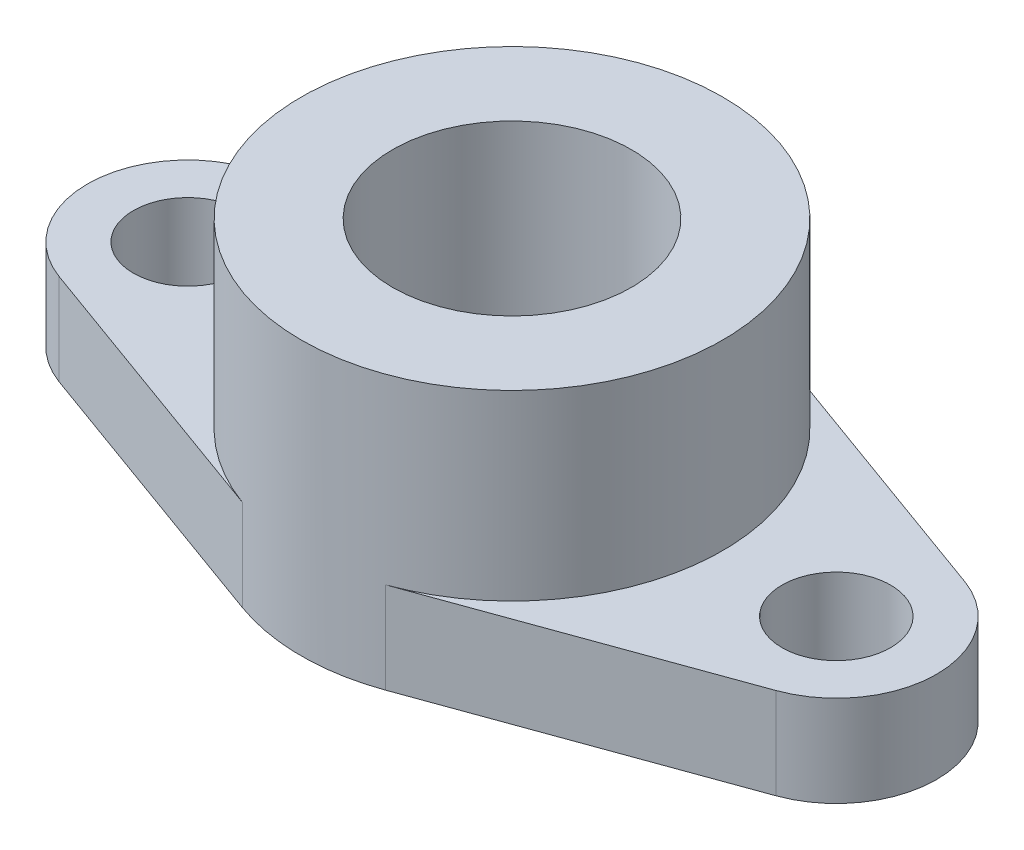
SolidWorks part; units mm, degrees
ref_plane "Front Plane" through (0, 0, 0) normal (0, 0, 1) x (1, 0, 0)
ref_plane "Top Plane" through (0, 0, 0) normal (0, 1, 0) x (1, 0, 0)
ref_plane "Right Plane" through (0, 0, 0) normal (1, 0, 0) x (0, 0, -1)
sketch "Sketch1" plane through (0, 0, 0) normal (0, 1, 0) x (1, 0, 0)
  line L0 (0, 0) -> (6.5484, 0) construction
  line L1 (0, 0) -> (17.78, 0) construction
  line L2 (19.651, 5.172) -> (3.9286, 10.8597)
  line L3 (3.9286, -10.8597) -> (19.651, -5.172)
  line L4 (0, 0) -> (-17.78, 0) construction
  line L5 (-19.651, 5.172) -> (-3.9286, 10.8597)
  line L6 (-19.651, -5.172) -> (-3.9286, -10.8597)
  circle A0 centre (0, 0) radius 4.826
  circle A1 centre (0, 0) radius 6.5484 construction
  arc A2 (3.9286, 10.8597) -> (3.9286, -10.8597) centre (0, 0) ccw construction
  circle A3 centre (17.78, 0) radius 2.9766
  arc A4 (19.651, -5.172) -> (19.651, 5.172) centre (17.78, 0) ccw
  circle A5 centre (0, 0) radius 11.5484 construction
  circle A6 centre (-17.78, 0) radius 2.9766
  arc A7 (-19.651, 5.172) -> (-19.651, -5.172) centre (-17.78, 0) ccw
  arc A10 (-3.9286, -10.8597) -> (3.9286, -10.8597) centre (0, 0) ccw
  arc A11 (3.9286, 10.8597) -> (-3.9286, 10.8597) centre (0, 0) ccw
  dimension "D1" = 9.652
  dimension "D2" = 13.0969
  dimension "D3" = 23.0969
  dimension "D5" = 5.9531
  dimension "D7" = 5.9531
  dimension "D6" = 5.5
  dimension "D4" = 17.78
  dimension "D8" = 17.78
extrude "Boss-Extrude1" add sketch "Sketch1" along normal blind 5
sketch "Sketch2" plane through (0, 5, 0) normal (0, 1, 0) x (1, 0, 0)
  circle A0 centre (0, 0) radius 11.5484
  arc A1 (-3.9286, -10.8597) -> (3.9286, -10.8597) centre (0, 0) ccw construction
  circle A2 centre (0, 0) radius 6.5484
  dimension "D1" = 13.0969
extrude "Boss-Extrude2" add sketch "Sketch2" along normal blind 10
equation "\"z\" = 8\t\t\t\t'number of blades"
equation "\"de\" = 0.43in\t\t\t'entrance eye diameter"
equation "\"de_length\" = 10mm\t\t'entrance eye consistent length"
equation "\"d_exit\" = 0.18in \t\t'throat aka d1"
equation "\"d2\" = 2.1in \t\t\t'outer diameter of the impeller"
equation "\"b2\" = .2in\t\t\t'tip height from disc surface at d2; slightly higher than d_exit"
equation "\"b1\" = \"b2\" + (\"d2\"/2 - \"de\"/2)*tan(\"theta\") \t\t\t'tip height from disc surface at inlet eye"
equation "\"theta\" = 12\t\t\t'angle of blades from inner to outer "
equation "\"ae\" = 3.14*(\"de\"^2)/4\t\t'entrance eye area'"
equation "\"ce\" = 3.14*\"de\"\t\t'entrance eye circumference"
equation "\"av_ratio\" = .325\t\t'ratio of av/ae at N_s of 470, range is .275 to .375, .325 ideal. High ratio means bigger area means smaller blades"
equation "\"av\" = \"ae\"*\"av_ratio\"\t\t'area between just two blades"
equation "\"s_open\" = \"av\"/\"b1\"\t\t'width of open area"
equation "\"s\"=\"ce\" - \"z\"*\"s_open\""
equation "\"min blade thickness\" = .15in"
equation "\"bearing OD\" = 30mm"
equation "\"bearing ID\"= 10mm"
equation "\"bearing depth\"= 9mm"
equation "\"bearing outer race thickness\"= 1mm"
equation "\"bearing inner race thickness\"= 1mm"
equation "\"bearing bore\" = \"bearing depth\" + 1mm"
equation "\"lower seal OD\" = .917in\t\t'this is https://www.mcmaster.com/#9281k121/=174001b"
equation "\"lower seal ID\"= .375in"
equation "\"lower seal depth\" = .625in + .218in"
equation "\"lower seal bore\" = \"lower seal depth\" + 1mm"
equation "\"upper seal OD\" = 1.125in\t'this is https://www.mcmaster.com/#5154t33/=173zuau, needs to be visually inspected before machining!"
equation "\"upper seal ID\"= 0.625in"
equation "\"upper seal depth\"= .25in\t'aka height; these values need to be confirmed by inspection!! We may want to compress the height."
equation "\"upper seal bore\" = \"upper seal depth\" + 1mm"
equation "\"big o-ring thickness\" = .139in"
equation "\"big o-ring OD\" = 2.734in"
equation "\"big o-ring ID\" = 3.012in"
equation "\"big o-ring groove depth\" = \"big o-ring thickness\"*4/5"
equation "\"impeller center height\" = \"impeller base thickness\" + \"b1\"\t'impeller height at de"
equation "\"impeller outer height\" = \"impeller base thickness\" + \"b2\"\t'impeller height at de"
equation "\"impeller upper clearance\"= .5mm"
equation "\"impeller horizontal clearance\"= (\"d2\"*1.15 - \"d2\")/2 \t\t'clearance based on D2-D3 ratio for circular volute, ranges 1.15 to 1.2"
equation "\"impeller bottom clearance\"= .5mm"
equation "\"impeller base thickness\"= 2mm"
equation "\"impeller dowel diameter\" = 2mm"
equation "\"impeller bolt head diameter\" = \"m4 head bore diameter\""
equation "\"impeller bolt head depth\" = 4mm"
equation "\"impeller bolt stop depth\" = 3mm"
equation "\"impeller bolt bore\" = \"m4 clearance\""
equation "\"impeller shaft bore depth\" = 12mm"
equation "\"impeller shaft bore\" = 8mm"
equation "\"impeller boss depth\" = \"impeller shaft bore depth\"+\"impeller bolt stop depth\"+\"impeller bolt head depth\"-\"impeller base thickness\""
equation "\"impeller boss diameter\" = \"upper seal ID\""
equation "\"impeller dowel length\" = 2mm*2 + \"impeller shaft bore\""
equation "\"coupler motor shaft hole ID\"= 8mm"
equation "\"coupler OD\"= 17mm"
equation "\"coupler length\"= 25mm"
equation "\"motor OD\" = 64mm"
equation "\"motor shaft diameter\"= 8mm"
equation "\"motor shaft pride\"= 32mm"
equation "\"motor to bearing plate distance\" = \"motor shaft pride\" + 2mm +\"coupler length\"/2"
equation "\"square plate bolt bore\" = \"m8 clearance\""
equation "\"square plate bolt head diameter\" = 13.5mm"
equation "\"square plate bolt head depth\" = 8mm"
equation "\"square plate bolt pattern diameter\"= 3.5in"
equation "\"motor mount center bore\"= \"coupler OD\"+ 4mm"
equation "\"motor mount post radius\"= ( 3 * \"square plate bolt bore\" ) / 2"
equation "\"motor mount m4 screw hole diameter\"= 4mm"
equation "\"motor mount m4 head diameter\"= 7.25mm"
equation "\"motor mount m4 head depth\"= 4mm"
equation "\"motor mount m4 pattern diamater\" = 30mm"
equation "\"motor mount plate thickness\"= 8mm + \"motor mount m4 head depth\""
equation "\"bearing plate stop ID\" = \"bearing OD\" - 4mm"
equation "\"bearing plate stop depth\" = 3mm"
equation "\"bearing plate thickness\" = \"bearing bore\" + \"bearing plate stop depth\" + \"shaft bearing stop length\""
equation "\"lower seal plate lip depth\" = 2mm"
equation "\"lower seal plate lip ID\" = \"lower seal OD\" - 3mm"
equation "\"lower seal plate thickness\" = \"lower seal plate lip depth\" + \"lower seal bore\""
equation "\"shaft coupler section diameter\" = 8mm"
equation "\"shaft coupler section length\" = \"motor to bearing plate distance\" - \"motor shaft pride\" - 2mm"
equation "\"shaft bearing section diameter\" = \"bearing ID\""
equation "\"shaft bearing section length\" = \"bearing plate stop depth\" + \"bearing depth\""
equation "\"shaft bearing stop diameter\" = \"bearing ID\" + 4mm"
equation "\"shaft bearing stop length\" = 3mm"
equation "\"shaft lower seal section diameter\" = \"lower seal ID\""
equation "\"shaft lower seal section length\" = \"lower seal plate thickness\" + 1mm"
equation "\"shaft impeller section diameter\" = \"impeller shaft bore\""
equation "\"shaft impeller section length\" = \"upper seal plate thickness\" + \"upper seal plate riser\" + \"impeller bottom clearance\" + \"impeller base thickness\" - \"impeller bolt head depth\" - \"impeller bolt stop depth\""
equation "\"upper seal plate thickness\" = \"upper seal plate pressure hole diameter\"+10mm"
equation "\"upper seal plate lip ID\" = \"upper seal OD\" - 3mm"
equation "\"upper seal plate riser\" = 6.59mm \t\t'this number needs to be read from the housing file"
equation "\"upper seal plate pressure hole diameter\" = .125in\t'this is 1/8 drill "
equation "\"upper seal plate pressure tap diameter\" = .328125in \t'this is 21/64 drill for a 1/8 ANPT tap"
equation "\"upper seal plate pressure tap grip\" = 5mm\t\t'this is the area around the tap so it doesn't crack"
equation "\"upper seal plate pressure tap depth\" = 12mm"
equation "\"impeller cavity center height\"= \"impeller bottom clearance\" + \"impeller upper clearance\" + \"impeller center height\""
equation "\"impeller cavity diameter\"= 2 * \"impeller horizontal clearance\" + \"d2\" \t\t\t\t\t\t\t\t\t'called D3 analytically"
equation "\"impeller cavity outer height\"= \"impeller bottom clearance\" + \"impeller upper clearance\" + \"impeller base thickness\" + \"b2\" \t\t'this is height at impeller diameter d2, not at d3"
equation "\"impeller housing thickness\"= \"impeller housing exit threaded diameter\" + 2*\"impeller housing outlet grip\""
equation "\"impeller housing diameter\" = \"square plate bolt pattern diameter\" + 2*\"motor mount post radius\""
equation "\"impeller housing bolt count\" = 6"
equation "\"impeller housing bolt diameter\" = \"m6 clearance\""
equation "\"impeller housing bolt pattern diameter\" = 3.5in"
equation "\"impeller housing threaded inlet diameter\" = 0.515625in \t'this is the 33/64 drill size for 9/16-18 fitting, expecting swagelok SS-8FK0-1-6STH fitting"
equation "\"impeller housing threaded inlet depth\"= 10mm"
equation "\"impeller housing exit threaded diameter\"= 0.515625in \t\t'this is the 33/64 drill size for 9/16-18 fitting, expecting swagelok SS-8FK0-1-6STH fitting"
equation "\"impeller housing exit threaded depth\"= 10mm"
equation "\"impeller housing diffuser conical angle\"=10"
equation "\"impeller housing diffuser tangent angle\"=5"
equation "\"impeller housing diffuser final diameter\" = .38in\t\t'aka d2'"
equation "\"impeller housing outlet grip\" = 5mm"
equation "\"end mill size\" = 0.375in\t'for 3/8 endmill"
equation "\"m4 clearance\" = 0.171875in \t'this is 11/64 bit for 4.36mm"
equation "\"m4 tap\" = 0.125in\t\t'this is 1/8 bit for 3.17mm"
equation "\"m4 head bore diameter\" = 7.5mm"
equation "\"m4 head bore depth\" = 5mm\t'actual is ~4mm"
equation "\"m6 clearance\" = 0.234375in\t'this is 15/64 bit = 5.95mm, could use 6mm bit, B bit for 6.04mm or 1/4 bit for 6.35mm"
equation "\"m6 tap\" = 5mm\t\t\t'5mm is appropriate, could use 13/64 or #5,6,7"
equation "\"m6 head bore diameter\" = 11mm\t\t"
equation "\"m6 head bore depth\" = 7mm\t'actual is 6mm"
equation "\"m8 clearance\" = 0.3125in\t'this is 5/16in for 7.93mm, could use 8mm, O,P, or 21/64"
equation "\"m8 tap\" = 0.265625in\t\t'this is 17/64 for 6.746875mm"
equation "\"m8 head bore diameter\" = 14mm"
equation "\"m8 head bore depth\" = 9mm\t'actual is 8mm"
equation "\"D1@Sketch1\"=\"impeller housing diffuser final diameter\""
equation "\"D2@Sketch1\"=\"impeller housing exit threaded diameter\""
equation "\"D3@Sketch1\"=\"impeller housing exit threaded diameter\"+\"impeller housing outlet grip\"*2 "
equation "\"D5@Sketch1\"=\"m6 clearance\""
equation "\"D7@Sketch1\"=\"m6 clearance\""
equation "\"D6@Sketch1\"=\"m6 head bore diameter\"/2"
equation "\"D1@Sketch2\"=\"impeller housing exit threaded diameter\""
equation "\"D1@Boss-Extrude2\"=10mm"
equation "\"diffuser cartridge OD\" =.75in"
equation "\"diffuser flange bolt pattern diameter\" = 1.4in"
equation "\"D4@Sketch1\"=\"diffuser flange bolt pattern diameter\"/2"
equation "\"D8@Sketch1\"=\"diffuser flange bolt pattern diameter\"/2"
